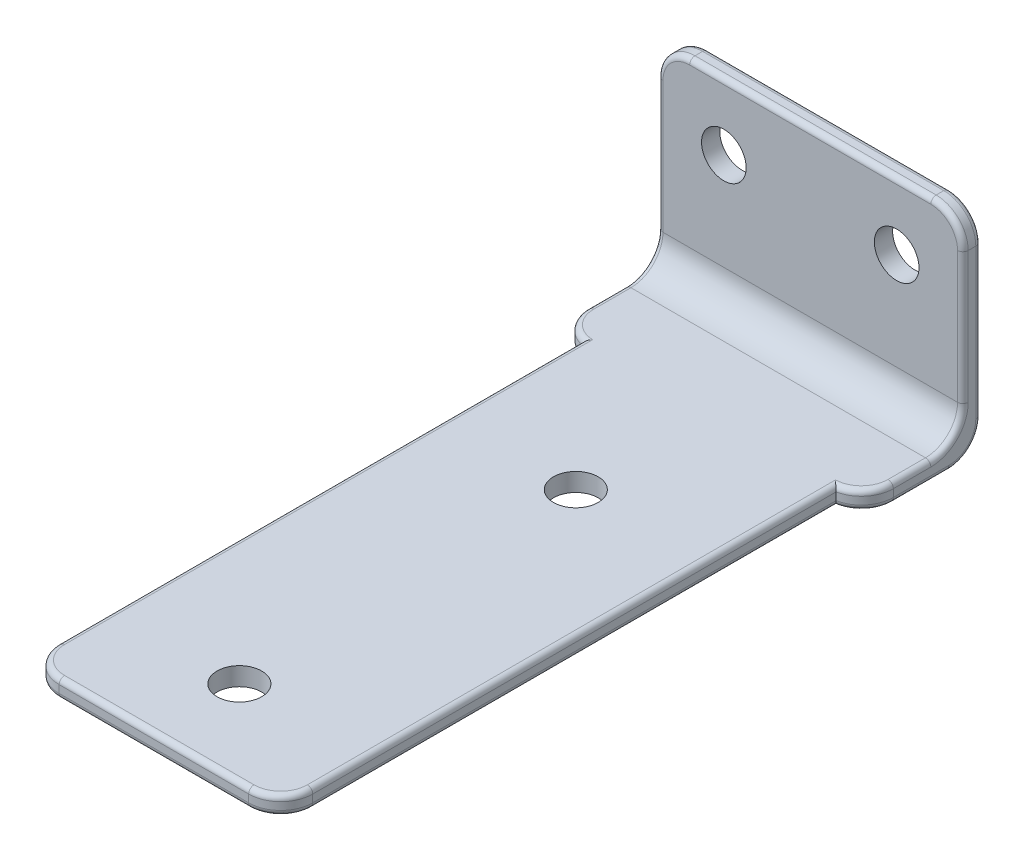
SolidWorks part; units mm, degrees
ref_plane "Front Plane" through (0, 0, 0) normal (0, 0, 1) x (1, 0, 0)
ref_plane "Top Plane" through (0, 0, 0) normal (0, 1, 0) x (1, 0, 0)
ref_plane "Right Plane" through (0, 0, 0) normal (1, 0, 0) x (0, 0, -1)
sketch "Sketch1" plane through (0, 0, 0) normal (0, 1, 0) x (1, 0, 0)
  line L1 (18.1483, -40.1066) -> (-18.1483, -40.1066)
  line L2 (18.1483, -40.1066) -> (18.1483, 40.1066)
  line L3 (18.1483, 40.1066) -> (-18.1483, 40.1066)
  line L4 (-18.1483, -40.1066) -> (-18.1483, 40.1066)
  line L5 (18.1483, -40.1066) -> (-18.1483, 40.1066) construction
  line L6 (18.1483, 40.1066) -> (-18.1483, -40.1066) construction
  point P0 (0, 0)
  dimension "D1" = 80.2132
  dimension "D2" = 36.2966
extrude "Boss-Base" add sketch "Sketch1" along normal blind 2.1717
sketch "Sketch3" plane through (0, 2.1717, 0) normal (0, 1, 0) x (1, 0, 0)
  line L0 (18.1483, -40.1066) -> (18.1483, 40.1066) construction
  line L1 (-18.1483, 40.1066) -> (18.1483, 40.1066)
  line L2 (-18.1483, 40.1066) -> (-18.1483, 37.9349)
  line L3 (-18.1483, 37.9349) -> (18.1483, 37.9349)
  line L4 (18.1483, 40.1066) -> (18.1483, 37.9349)
  dimension "D1" = 2.1717
extrude "Boss-Lip" add sketch "Sketch3" along normal blind 23.2512
sketch "Base Centerline" plane through (0, 2.1717, 0) normal (0, 1, 0) x (1, 0, 0)
  line L0 (0, -40.1066) -> (0, 40.1066) construction
  line L1 (-18.1483, -40.1066) -> (18.1483, -40.1066) construction
  line L2 (18.1483, 40.1066) -> (-18.1483, 40.1066) construction
  point P6 (0, -29.9466)
  point P7 (0, 10.0584)
  dimension "D1" = 10.16
  dimension "D2" = 50.165
hole_wizard "#4 (0.209) Diameter Hole1" positions "Sketch5" profile "Sketch6" hole size "#4" standard "ANSI Inch" end condition through all
sketch "Sketch5" plane through (0, 2.1717, 0) normal (0, 1, 0) x (1, 0, 0)
  point P0 (0, -29.9466)
  point P3 (0, 10.0584)
sketch "Sketch6" plane through (0, 2.1717, 29.9466) normal (1, 0, 0) x (0, 0, 1)
  line L0 (0, 0) -> (0, 2.1717)
  line L1 (0, 2.1717) -> (2.6543, 2.1717)
  line L2 (2.6543, 2.1717) -> (2.6543, 0)
  line L5 (2.6543, 0) -> (0, 0)
  line L11 (0, -6.35) -> (0, 107.95) construction
  dimension "Thru Hole Dia." = 5.3086
  dimension "Thru Hole Depth" = 2.1717
sketch "Sketch7" plane through (0, 0, -37.9349) normal (0, 0, 1) x (1, 0, 0)
  line L0 (-18.1483, 25.4229) -> (18.1483, 25.4229) construction
  line L1 (-18.1483, 25.4229) -> (-18.1483, 2.1717) construction
  line L2 (18.1483, 25.4229) -> (18.1483, 2.1717) construction
  point P0 (10.2743, 17.5489)
  point P1 (-10.2743, 17.5489)
  dimension "D1" = 7.874
  dimension "D2" = 7.874
  dimension "D3" = 7.874
  dimension "D4" = 7.874
hole_wizard "#4 (0.209) Diameter Hole2" positions "Sketch7" profile "Sketch8" hole size "#4" standard "ANSI Inch" end condition through all
sketch "Sketch8" plane through (10.2743, 17.5489, -37.9349) normal (1, 0, 0) x (0, -1, 0)
  line L0 (0, 0) -> (0, 2.1717)
  line L1 (0, 2.1717) -> (2.6543, 2.1717)
  line L2 (2.6543, 2.1717) -> (2.6543, 0)
  line L5 (2.6543, 0) -> (0, 0)
  line L11 (0, -6.35) -> (0, 107.95) construction
  dimension "Thru Hole Dia." = 5.3086
  dimension "Thru Hole Depth" = 2.1717
sketch "Sketch19" plane through (0, 2.1717, 0) normal (0, 1, 0) x (1, 0, 0)
  line L0 (0, 40.1066) -> (0, -40.1066) construction
  line L1 (18.1483, -40.1066) -> (15.0749, -40.1066)
  line L2 (18.1483, -40.1066) -> (18.1483, 25.9334)
  line L3 (18.1483, 25.9334) -> (15.0749, 25.9334)
  line L4 (15.0749, -40.1066) -> (15.0749, 25.9334)
  line L6 (-18.1483, -40.1066) -> (-15.0749, -40.1066)
  line L7 (-18.1483, -40.1066) -> (-18.1483, 25.9334)
  line L8 (-18.1483, 25.9334) -> (-15.0749, 25.9334)
  line L9 (-15.0749, -40.1066) -> (-15.0749, 25.9334)
  dimension "D1" = 3.0734
  dimension "D2" = 66.04
  dimension "D3" = 3.0734
extrude "Cut-Extrude1" cut sketch "Sketch19" against normal through all
fillet "Fillet1" radius 3.81 8 edges at (-18.1483, 1.0858, -25.9334) (18.1483, 1.0858, -25.9334) (15.0749, 1.0858, 40.1066) (-15.0749, 1.0858, 40.1066) (-18.1483, 25.4229, -39.0208) (18.1483, 25.4229, -39.0208) (0, 0, -40.1066) (0, 2.1717, -37.9349)
fillet "Fillet4" radius 0.635 32 edges at (17.0324, 24.3069, -37.9349) (-17.0324, 24.3069, -37.9349) (17.0324, 24.3069, -40.1066) (-17.0324, 24.3069, -40.1066) (13.959, 0, 38.9907) (-13.959, 0, 38.9907) (13.959, 2.1717, 38.9907) (-13.959, 2.1717, 38.9907) (18.1483, 13.7973, -37.9349) (18.1483, 12.7114, -40.1066) (0, 25.4229, -37.9349) (0, 25.4229, -40.1066) (-18.1483, 13.7973, -37.9349) (-18.1483, 12.7114, -40.1066) (0, 0, 40.1066) (0, 2.1717, 40.1066) (15.0749, 0, 5.1816) (15.0749, 2.1717, 5.1816) (-15.0749, 0, 5.1816) (-15.0749, 2.1717, 5.1816) (17.2813, 0, -27.2518) (-17.2813, 0, -27.2518) (-17.2813, 2.1717, -27.2518) (18.1483, 0, -32.9841) (-18.1483, 0, -32.9841) (-18.1483, 2.1717, -31.8982) (17.2813, 2.1717, -27.2518) (18.1483, 2.1717, -31.8982) (18.1483, 1.1159, -38.9907) (-18.1483, 1.1159, -38.9907) (18.1483, 3.2876, -36.819) (-18.1483, 3.2876, -36.819)
